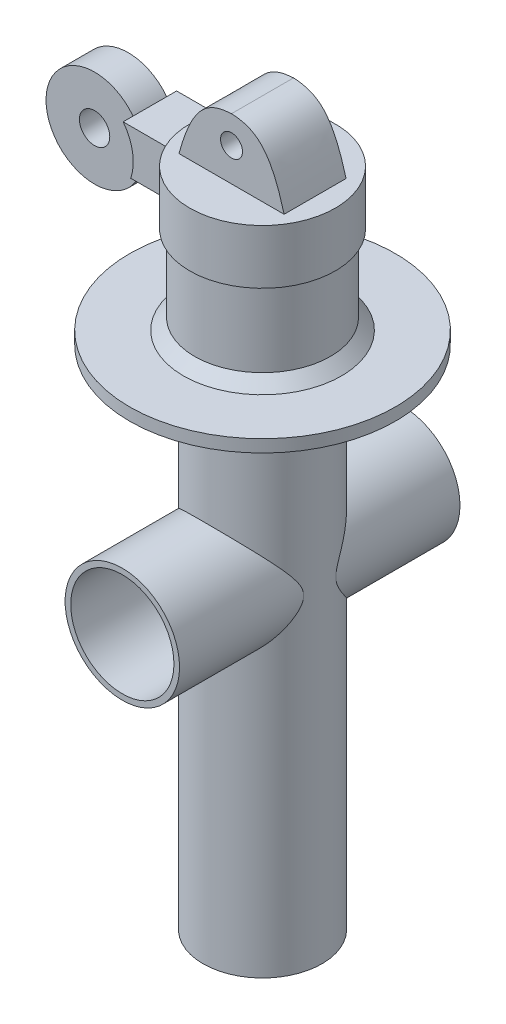
SolidWorks part; units mm, degrees
ref_plane "Front" through (0, 0, 0) normal (0, 0, 1) x (1, 0, 0)
ref_plane "Top" through (0, 0, 0) normal (0, 1, 0) x (1, 0, 0)
ref_plane "Right" through (0, 0, 0) normal (1, 0, 0) x (0, 0, -1)
ref_plane "Plane1" through (0, 0, -1) normal (0, 0, 1) x (1, 0, 0)
ref_plane "Plane2" through (0, 0, 10) normal (0, 0, 1) x (1, 0, 0)
sketch "Sketch2" plane through (0, 0, -1) normal (0, 0, 1) x (1, 0, 0)
  line L0 (-159.4387, 154.3507) -> (137.2047, 154.3507) construction
  line L1 (-404.2477, -195.5851) -> (-112.1409, -116.2103) construction
sketch "Sketch6" plane through (0, 0, 0) normal (0, 0, 1) x (1, 0, 0)
  line L0 (0, 0) -> (0, 27.8802) construction
  line L1 (-21.1979, 0) -> (21.1979, 0)
  line L2 (-21.1979, 0) -> (-21.1979, 180.6476)
  line L3 (-21.1979, 180.6476) -> (21.1979, 180.6476)
  line L4 (21.1979, 0) -> (21.1979, 180.6476)
  line L5 (-47.3805, 180.6476) -> (47.3805, 180.6476)
  line L6 (-47.3805, 180.6476) -> (-47.3805, 185.0788)
  line L7 (-47.3805, 185.0788) -> (47.3805, 185.0788)
  line L8 (47.3805, 180.6476) -> (47.3805, 185.0788)
  line L9 (-47.3805, 180.6476) -> (47.3805, 185.0788) construction
  line L10 (-47.3805, 185.0788) -> (47.3805, 180.6476) construction
  line L12 (-24.2143, 185.0788) -> (24.2143, 185.0788)
  line L13 (-24.2143, 185.0788) -> (-24.2143, 216.3885)
  line L14 (-24.2143, 216.3885) -> (24.2143, 216.3885)
  line L15 (24.2143, 185.0788) -> (24.2143, 216.3885)
  line L16 (-24.2143, 185.0788) -> (24.2143, 216.3885) construction
  line L17 (-24.2143, 216.3885) -> (24.2143, 185.0788) construction
  line L18 (-25.9834, 216.3885) -> (25.9834, 216.3885)
  line L19 (-25.9834, 216.3885) -> (-25.9834, 235.7838)
  line L20 (-25.9834, 235.7838) -> (25.9834, 235.7838)
  line L21 (25.9834, 216.3885) -> (25.9834, 235.7838)
  line L22 (-25.9834, 216.3885) -> (25.9834, 235.7838) construction
  line L23 (-25.9834, 235.7838) -> (25.9834, 216.3885) construction
  point P4 (0, 182.8632)
  point P11 (0, 200.7337)
  point P16 (0, 226.0862)
  dimension "D1" = 42.3958
  dimension "D2" = 180.6476
  dimension "D3" = 31.3098
  dimension "D4" = 51.9668
  dimension "D5" = 94.7609
  dimension "D6" = 48.4286
  dimension "D7" = 19.3952
  dimension "D8" = 4.4312
sketch "Sketch7" plane through (0, 0, 0) normal (0, 1, 0) x (1, 0, 0)
  circle A0 centre (0, 0) radius 21.1979
extrude "Boss-Extrude1" add sketch "Sketch7" along normal up to vertex (180.6476 mm away) up to point (-21.1979, 180.6476, 0)
sketch "Sketch12" plane through (0, 0, 0) normal (0, 0, 1) x (1, 0, 0)
  circle A0 centre (0, 116.1951) radius 20.407
extrude "Boss-Extrude6" add sketch "Sketch12" against normal mid plane 100
shell "Shell1" thickness 2 removed face at (20.407, 116.1951, -50) removed face at (20.407, 116.1951, 50) removed face at (0, 0, 21.1979)
sketch "Sketch8" plane through (0, 180.6476, 0) normal (0, 1, 0) x (1, 0, 0)
  line L0 (-21.1979, 0) -> (21.1979, 0) construction
  circle A0 centre (0, 0) radius 47.3805
extrude "Boss-Extrude2" add sketch "Sketch8" along normal up to vertex (4.4312 mm away) up to point (47.3805, 185.0788, 0)
sketch "Sketch9" plane through (0, 185.0788, 0) normal (0, 1, 0) x (1, 0, 0)
  circle A0 centre (0, 0) radius 24.2143
extrude "Boss-Extrude3" add sketch "Sketch9" along normal up to vertex (31.3098 mm away) up to point (24.2143, 216.3885, 0)
sketch "Sketch10" plane through (0, 216.3885, 0) normal (0, 1, 0) x (1, 0, 0)
  line L0 (-24.2143, 0) -> (24.2143, 0) construction
  circle A0 centre (0, 0) radius 25.9834
extrude "Boss-Extrude4" add sketch "Sketch10" along normal up to vertex (19.3952 mm away) up to point (25.9834, 235.7838, 0)
chamfer "Chamfer1" distance 4 angle 45 1 edges at (0, 185.0788, 24.2143)
sketch "Sketch11" plane through (0, 0, 0) normal (0, 0, 1) x (1, 0, 0)
  line L0 (-25.9834, 235.7838) -> (25.9834, 235.7838) construction
  line L1 (-18.7469, 235.7838) -> (18.3942, 235.7838) construction
  line L2 (0, 226.0862) -> (0, 257.4912) construction
  line L3 (-18.7469, 235.7838) -> (18.7469, 235.7838)
  line L5 (3.6287, 253.9667) -> (-3.6287, 253.9667) construction
  line L6 (-3.6287, 253.9667) -> (-7.2574, 247.6816) construction
  line L7 (-7.2574, 247.6816) -> (-3.6287, 241.3965) construction
  line L8 (-3.6287, 241.3965) -> (3.6287, 241.3965) construction
  line L9 (3.6287, 241.3965) -> (7.2574, 247.6816) construction
  line L10 (7.2574, 247.6816) -> (3.6287, 253.9667) construction
  circle A0 centre (0, 247.6816) radius 6.2851 construction
  circle A1 centre (0, 247.6816) radius 3.9097
  spline S0 degree 3 poles (-18.7469, 235.7838) (-13.8887, 253.686) (-8.2939, 257.0146) (0, 257.4912) knots 0 0 0 0 0.516374 0.516374 0.516374 0.516374
  spline S1 degree 3 poles (18.7469, 235.7838) (13.8887, 253.686) (8.2939, 257.0146) (0, 257.4912) knots 0 0 0 0 0.516374 0.516374 0.516374 0.516374
  dimension "D1" = 2.3754
  dimension "D2" = 7.8194
extrude "Boss-Extrude5" add sketch "Sketch11" against normal mid plane 22.1
sketch "Sketch13" plane through (0, 0, 0) normal (1, 0, 0) x (0, 0, -1)
  line L0 (0, 235.7838) -> (0, 216.3885) construction
  line L1 (-9.5324, 218.0483) -> (9.5324, 218.0483)
  line L2 (-9.5324, 218.0483) -> (-9.5324, 234.124)
  line L3 (-9.5324, 234.124) -> (9.5324, 234.124)
  line L4 (9.5324, 218.0483) -> (9.5324, 234.124)
  line L5 (-9.5324, 218.0483) -> (9.5324, 234.124) construction
  line L6 (-9.5324, 234.124) -> (9.5324, 218.0483) construction
  line L7 (11.05, 235.7838) -> (-11.05, 235.7838) construction
  point P0 (0, 226.0862)
extrude "Boss-Extrude7" add sketch "Sketch13" against normal blind 52
sketch "Sketch14" plane through (0, 0, 0) normal (0, 0, 1) x (1, 0, 0)
  line L0 (-63.4623, 237.988) -> (-56.8808, 228.0651)
  line L1 (-37.4696, 218.0483) -> (-52, 218.0483)
  line L2 (-52, 218.0483) -> (-52, 234.124)
  line L3 (-52, 234.124) -> (-40.1694, 234.124)
  line L4 (-52, 234.124) -> (-52, 218.0483) construction
  line L5 (-52, 234.124) -> (-24.1717, 234.124) construction
  circle A0 centre (-53.8896, 223.5552) radius 17.3189
  circle A1 centre (-53.8896, 223.5552) radius 5.4117
  circle A2 centre (-53.8896, 223.5552) radius 11.6368
extrude "Cut-Extrude1" cut sketch "Sketch14" against normal mid plane 52 contours L1 A1 L2 | L1 A2 L3 L2 A1 | A2 L1 A0 L3 region at (-40.6946, 226.4906, 0) region at (-46.9684, 225.8097, 0) region at (-50.5426, 223.5552, 0)
extrude "Boss-Extrude9" add sketch "Sketch14<5>" along normal mid plane 12 contours L2 A1 | L2 A1 | A2 L3 A0 L0 | A2 L0 A0 L1 | A2 L1 A0 L3 | A2 region at (-52.6469, 237.1785, 0) region at (-62.2781, 235.3644, 0) region at (-40.6946, 226.4906, 0) region at (-55.2062, 223.5552, 0) region at (-50.5426, 223.5552, 0)
sketch "Sketch14<5>" plane through (0, 0, 0) normal (0, 0, 1) x (1, 0, 0) same geometry as "Sketch14"
